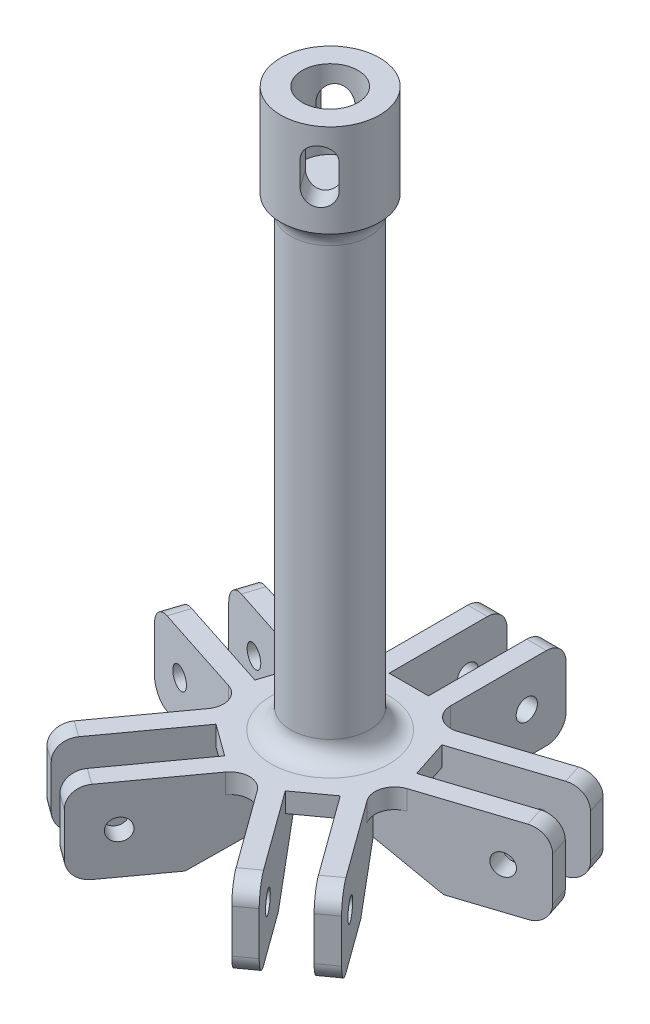
SolidWorks part; units mm, degrees
material "ABS PC"
ref_plane "Front Plane" through (0, 0, 0) normal (0, 0, 1) x (1, 0, 0)
ref_plane "Top Plane" through (0, 0, 0) normal (0, 1, 0) x (1, 0, 0)
ref_plane "Right Plane" through (0, 0, 0) normal (1, 0, 0) x (0, 0, -1)
sketch "Sketch1" plane through (0, 0, 0) normal (0, 1, 0) x (1, 0, 0)
  line L0 (-3.175, 17.78) -> (3.175, 17.78)
  line L1 (15.9287, 8.5139) -> (17.8909, 2.4747)
  line L2 (13.0195, -12.5181) -> (7.8822, -16.2505)
  line L3 (28.2338, 15.8505) -> (14.6623, 11.4408)
  line L4 (3.175, 31.75) -> (6.35, 31.75)
  line L5 (29.2149, 12.8309) -> (15.9287, 8.5139)
  line L6 (-7.8822, -16.2505) -> (-13.0195, -12.5181)
  line L7 (-15.9287, 8.5139) -> (-17.8909, 2.4747)
  line L8 (28.2338, 15.8505) -> (16.1554, 11.926)
  line L9 (-23.7994, -21.9539) -> (-12.8431, -6.8738)
  line L10 (-6.35, 31.75) -> (-6.35, 17.4801)
  line L11 (-13.5249, -29.4187) -> (-2.5686, -14.3387)
  line L12 (-3.175, 31.75) -> (-3.175, 17.78)
  line L13 (-31.1772, 6.7917) -> (-32.1583, 3.7721)
  line L14 (-6.35, 31.75) -> (-6.35, 17.78)
  line L15 (-29.2149, 12.8309) -> (-28.2338, 15.8505)
  line L16 (3.175, 31.75) -> (3.175, 17.78)
  line L17 (6.35, 31.75) -> (6.35, 21.59)
  line L18 (13.5249, -29.4187) -> (2.5686, -14.3387)
  line L19 (6.35, 31.75) -> (6.35, 17.4801)
  line L20 (31.1772, 6.7917) -> (17.8909, 2.4747)
  line L21 (32.1583, 3.7721) -> (22.4956, 0.6325)
  line L22 (-6.35, 31.75) -> (-3.175, 31.75)
  line L23 (32.1583, 3.7721) -> (18.5868, -0.6376)
  line L24 (-16.0936, -27.5525) -> (-13.5249, -29.4187)
  line L25 (-23.7994, -21.9539) -> (-21.2308, -23.8201)
  line L26 (23.7994, -21.9539) -> (15.4118, -10.4092)
  line L27 (23.7994, -21.9539) -> (12.8431, -6.8738)
  line L28 (21.2308, -23.8201) -> (13.0195, -12.5181)
  line L29 (32.1583, 3.7721) -> (31.1772, 6.7917)
  line L30 (23.7994, -21.9539) -> (16.3346, -11.6793)
  line L31 (13.5249, -29.4187) -> (16.0936, -27.5525)
  line L32 (16.0936, -27.5525) -> (7.8822, -16.2505)
  line L33 (13.5249, -29.4187) -> (7.553, -21.1991)
  line L34 (29.2149, 12.8309) -> (28.2338, 15.8505)
  line L35 (13.5249, -29.4187) -> (5.1373, -17.8741)
  line L36 (21.2308, -23.8201) -> (23.7994, -21.9539)
  line L37 (32.1583, 3.7721) -> (14.4306, -1.988)
  line L38 (-13.5249, -29.4187) -> (-5.1373, -17.8741)
  line L39 (28.2338, 15.8505) -> (10.5061, 10.0904)
  line L40 (-16.0936, -27.5525) -> (-7.8822, -16.2505)
  line L41 (6.35, 31.75) -> (6.35, 13.11)
  line L42 (-13.5249, -29.4187) -> (-6.0601, -19.1442)
  line L43 (-6.35, 31.75) -> (-6.35, 13.11)
  line L44 (-21.2308, -23.8201) -> (-13.0195, -12.5181)
  line L45 (-23.7994, -21.9539) -> (-17.8275, -13.7342)
  line L46 (-28.2338, 15.8505) -> (-10.5061, 10.0904)
  line L47 (-23.7994, -21.9539) -> (-15.4118, -10.4092)
  line L48 (-32.1583, 3.7721) -> (-14.4306, -1.988)
  line L50 (-32.1583, 3.7721) -> (-18.5868, -0.6376)
  line L52 (-31.1772, 6.7917) -> (-17.8909, 2.4747)
  line L54 (-32.1583, 3.7721) -> (-20.0799, -0.1524)
  line L56 (-29.2149, 12.8309) -> (-15.9287, 8.5139)
  line L57 (-28.2338, 15.8505) -> (-18.5711, 12.7109)
  line L59 (-28.2338, 15.8505) -> (-14.6623, 11.4408)
  arc A0 (-14.4306, -1.988) -> (-12.8431, -6.8738) centre (-15.4118, -5.0076) cw
  arc A1 (-2.5686, -14.3387) -> (2.5686, -14.3387) centre (0, -16.2049) cw
  arc A2 (12.8431, -6.8738) -> (14.4306, -1.988) centre (15.4118, -5.0076) cw
  arc A3 (10.5061, 10.0904) -> (6.35, 13.11) centre (9.525, 13.11) cw
  arc A4 (-10.5061, 10.0904) -> (-6.35, 13.11) centre (-9.525, 13.11) ccw
  dimension "D1" = 3.175
  dimension "D2" = 5
  dimension "D4" = 3.175
  dimension "D6" = 3.175
  dimension "D3" = 6.35
extrude "Boss-Extrude1" add sketch "Sketch1" along normal blind 3.175 contours L10 L59 L57 L13 L56 L7 L52 L50 L47 L45 L44 L6 L40 L38 L35 L33 L32 L2 L28 L26 L23 L21 L20 L1 L5 L3 L19 L17 L16 L0 L12 region at (0, 0, 0)
sketch "Sketch2" plane through (0, 0, 0) normal (0, -1, 0) x (1, 0, 0)
  line L0 (-28.2338, -15.8505) -> (-29.2149, -12.8309)
  line L1 (-23.7994, 21.9539) -> (-21.2308, 23.8201)
  line L2 (-13.0195, 12.5181) -> (-15.5881, 10.6519)
  line L3 (-15.5881, 10.6519) -> (-23.7994, 21.9539)
  line L4 (-13.5249, 29.4187) -> (-16.0936, 27.5525)
  line L5 (-16.0936, 27.5525) -> (-7.8822, 16.2505)
  line L6 (-7.8822, 16.2505) -> (-5.3136, 18.1168)
  line L7 (-13.0195, 12.5181) -> (-21.2308, 23.8201)
  line L8 (-5.3136, 18.1168) -> (-13.5249, 29.4187)
  line L9 (13.5249, 29.4187) -> (16.0936, 27.5525)
  line L10 (-15.9287, -8.5139) -> (-14.9475, -11.5335)
  line L11 (-28.2338, -15.8505) -> (-10.5061, -10.0904) construction
  line L12 (-14.9475, -11.5335) -> (-28.2338, -15.8505)
  line L13 (-32.1583, -3.7721) -> (-31.1772, -6.7917)
  line L14 (-31.1772, -6.7917) -> (-17.8909, -2.4747)
  line L15 (-17.8909, -2.4747) -> (-18.872, 0.5449)
  line L16 (-32.1583, -3.7721) -> (-14.4306, 1.988) construction
  line L17 (7.8822, 16.2505) -> (5.3136, 18.1168)
  line L18 (5.3136, 18.1168) -> (13.5249, 29.4187)
  line L19 (23.7994, 21.9539) -> (21.2308, 23.8201)
  line L20 (21.2308, 23.8201) -> (13.0195, 12.5181)
  line L21 (13.0195, 12.5181) -> (15.5881, 10.6519)
  line L22 (7.8822, 16.2505) -> (16.0936, 27.5525)
  line L23 (15.5881, 10.6519) -> (23.7994, 21.9539)
  line L24 (32.1583, -3.7721) -> (31.1772, -6.7917)
  line L25 (17.8909, -2.4747) -> (18.872, 0.5449)
  line L26 (18.872, 0.5449) -> (32.1583, -3.7721)
  line L27 (28.2338, -15.8505) -> (29.2149, -12.8309)
  line L28 (29.2149, -12.8309) -> (15.9287, -8.5139)
  line L29 (15.9287, -8.5139) -> (14.9475, -11.5335)
  line L30 (17.8909, -2.4747) -> (31.1772, -6.7917)
  line L31 (14.9475, -11.5335) -> (28.2338, -15.8505)
  line L32 (6.35, -31.75) -> (3.175, -31.75)
  line L33 (3.175, -17.78) -> (6.35, -17.78)
  line L34 (6.35, -17.78) -> (6.35, -31.75)
  line L35 (-6.35, -31.75) -> (-3.175, -31.75)
  line L36 (-3.175, -31.75) -> (-3.175, -17.78)
  line L37 (-3.175, -17.78) -> (-6.35, -17.78)
  line L38 (-15.9287, -8.5139) -> (-29.2149, -12.8309)
  line L39 (-18.872, 0.5449) -> (-32.1583, -3.7721)
  line L41 (3.175, -17.78) -> (3.175, -31.75)
  line L42 (-6.35, -17.78) -> (-6.35, -31.75)
  point P48 (0, 0)
extrude "Boss-Extrude2" add sketch "Sketch2" along normal blind 10.16
fillet "Fillet1" radius 3.175 20 edges at (-31.6677, 3.175, -5.2819) (-22.5151, 3.175, 22.887) (-14.8092, 3.175, 28.4856) (-28.7244, 3.175, -14.3407) (4.7625, 3.175, -31.75) (-4.7625, 3.175, -31.75) (28.7244, 3.175, -14.3407) (31.6677, 3.175, -5.2819) (22.5151, 3.175, 22.887) (14.8092, 3.175, 28.4856) (28.7244, -10.16, -14.3407) (31.6677, -10.16, -5.2819) (4.7625, -10.16, -31.75) (-28.7244, -10.16, -14.3407) (-31.6677, -10.16, -5.2819) (22.5151, -10.16, 22.887) (14.8092, -10.16, 28.4856) (-14.8092, -10.16, 28.4856) (-22.5151, -10.16, 22.887) (-4.7625, -10.16, -31.75)
sketch "Sketch3" plane through (0, 3.175, 0) normal (0, 1, 0) x (1, 0, 0)
  circle A0 centre (0, 0) radius 6.35
extrude "Boss-Extrude3" add sketch "Sketch3" along normal blind 90
sketch "Sketch4" plane through (-6.35, 0, 0) normal (-1, 0, 0) x (0, 0, 1)
  line L0 (-28.575, 3.175) -> (-13.11, 3.175) construction
  line L2 (-31.75, 0) -> (-31.75, -6.985) construction
  circle A0 centre (-25.4, -3.4925) radius 1.7145
  dimension "D1" = 6.6675
  dimension "D2" = 3.429
  dimension "D3" = 6.35
extrude "Cut-Extrude1" cut sketch "Sketch4" against normal through all and the other way through all
pattern_circular "CirPattern2" count 5 over 360 about axis through (0, 93.175, 0) along (0, -1, 0) of "Cut-Extrude1"
sketch "Sketch5" plane through (0, 93.175, 0) normal (0, 1, 0) x (1, 0, 0)
  circle A0 centre (0, 0) radius 4.5
extrude "Cut-Extrude2" cut sketch "Sketch5" against normal blind 12.7
fillet "Fillet2" radius 3.175 1 edges at (0, 3.175, 6.35)
chamfer "Chamfer1" distance 3.175 angle 45 1 edges at (0, 3.175, -17.78)
sketch "Sketch6" plane through (0, 3.175, 0) normal (0, 1, 0) x (1, 0, 0)
  line L0 (17.8909, 2.4747) -> (15.9287, 8.5139)
  line L1 (3.175, 17.78) -> (-3.175, 17.78)
  line L2 (3.175, 17.78) -> (3.175, 12.7)
  line L3 (3.175, 12.7) -> (-3.175, 12.7)
  line L4 (-3.175, 17.78) -> (-3.175, 12.7)
  line L5 (17.8909, 2.4747) -> (13.0595, 0.9049)
  line L6 (13.0595, 0.9049) -> (11.0973, 6.9441)
  line L7 (15.9287, 8.5139) -> (11.0973, 6.9441)
  line L8 (7.8822, -16.2505) -> (13.0195, -12.5181)
  line L9 (7.8822, -16.2505) -> (4.8962, -12.1407)
  line L10 (4.8962, -12.1407) -> (10.0335, -8.4083)
  line L11 (13.0195, -12.5181) -> (10.0335, -8.4083)
  line L12 (-13.0195, -12.5181) -> (-7.8822, -16.2505)
  line L13 (-13.0195, -12.5181) -> (-10.0335, -8.4083)
  line L14 (-10.0335, -8.4083) -> (-4.8962, -12.1407)
  line L15 (-7.8822, -16.2505) -> (-4.8962, -12.1407)
  line L16 (-15.9287, 8.5139) -> (-17.8909, 2.4747)
  line L17 (-15.9287, 8.5139) -> (-11.0973, 6.9441)
  line L18 (-11.0973, 6.9441) -> (-13.0595, 0.9049)
  line L19 (-17.8909, 2.4747) -> (-13.0595, 0.9049)
  point P25 (0, 0)
  dimension "D1" = 5.08
  dimension "D2" = 5
extrude "Cut-Extrude3" cut sketch "Sketch6" against normal through all
sketch "Sketch7" plane through (5.1373, 0, -3.7324) normal (0.809, 0, -0.5878) x (-0.5878, 0, -0.809)
  line L0 (-17.78, -10.16) -> (0, 0)
  line L1 (0, 0) -> (-17.78, 0)
  line L2 (-17.78, 0) -> (-17.78, -10.16)
extrude "Boss-Extrude4" add sketch "Sketch7" against normal blind 3.175
sketch "Sketch8" plane through (-5.1373, 0, 3.7324) normal (-0.809, 0, 0.5878) x (0.5878, 0, 0.809)
  line L0 (17.78, -10.16) -> (0, 0)
  line L1 (0, 0) -> (17.78, 0)
  line L2 (17.78, 0) -> (17.78, -10.16)
extrude "Boss-Extrude5" add sketch "Sketch8" against normal blind 3.175
pattern_circular "CirPattern3" count 5 over 360 about axis through (0, 93.175, 0) along (0, -1, 0) of "Boss-Extrude5", "Boss-Extrude4"
sketch "Sketch10" plane through (0, 93.175, 0) normal (0, 1, 0) x (1, 0, 0)
  circle A0 centre (0, 0) radius 8
  circle A1 centre (0, 0) radius 6.35
extrude "Boss-Extrude6" add sketch "Sketch10" against normal blind 15
fillet "Fillet3" radius 3.175 1 edges at (0, 78.175, 6.35)
ref_plane "Plane1" through (0, 0, 0) normal (0.309, 0, 0.9511) x (0.9511, 0, -0.309)
ref_plane "Plane3" through (9.3311, 0, 12.8431) normal (0.5878, 0, 0.809) x (0.809, 0, -0.5878)
sketch "Sketch14" plane through (9.3311, 0, 12.8431) normal (0.5878, 0, 0.809) x (0.809, 0, -0.5878)
  line L0 (0, 93.175) -> (0, 90.425) construction
  line L1 (2.25, 88.175) -> (2.25, 84.075)
  line L2 (-2.25, 88.175) -> (-2.25, 84.075)
  line L3 (0, 81.825) -> (0, 78.175) construction
  line L4 (8, 93.175) -> (-8, 93.175) construction
  arc A0 (2.25, 88.175) -> (-2.25, 88.175) centre (0, 88.175) ccw
  arc A1 (-2.25, 84.075) -> (2.25, 84.075) centre (0, 84.075) ccw
  point P10 (0, 93.175)
  dimension "D2" = 2.25
  dimension "D3" = 2.25
  dimension "D1" = 4.1
  dimension "D4" = 2.75
  dimension "D5" = 3.65
extrude "Cut-Extrude6" cut sketch "Sketch14" against normal through all and the other way through all
